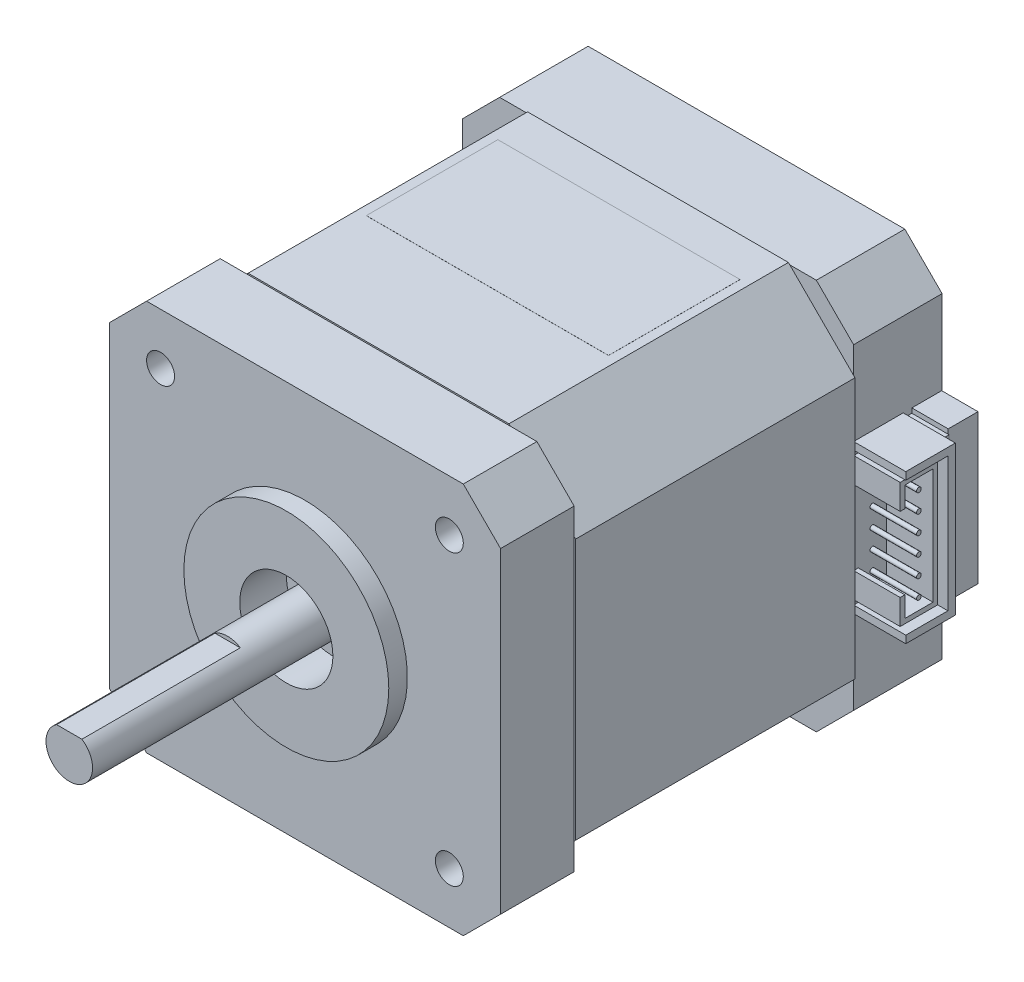
SolidWorks part; units mm, degrees
ref_plane "Front Plane" through (0, 0, 0) normal (0, 0, 1) x (1, 0, 0)
ref_plane "Top Plane" through (0, 0, 0) normal (0, 1, 0) x (1, 0, 0)
ref_plane "Right Plane" through (0, 0, 0) normal (1, 0, 0) x (0, 0, -1)
sketch "Sketch1" plane through (0, 0, 0) normal (0, 0, 1) x (1, 0, 0)
  line L0 (-17, 21) -> (-21, 17)
  line L1 (-17, -21) -> (17, -21)
  line L2 (-21, -17) -> (-21, 17)
  line L3 (-17, 21) -> (17, 21)
  line L4 (21, -17) -> (21, 17)
  line L5 (21, 17) -> (17, 21)
  line L6 (17, -21) -> (21, -17)
  line L12 (-21, -17) -> (-17, -21)
  point P0 (0, 0)
  point P15 (0, 0)
  dimension "D1" = 4
extrude "Boss-Extrude1" add sketch "Sketch1" along normal blind 9.5
sketch "Sketch2" plane through (0, 0, 9.5) normal (0, 0, 1) x (1, 0, 0)
  line L0 (14, 21.15) -> (21.15, 14)
  line L5 (-14, -21.15) -> (14, -21.15)
  line L6 (-21.15, -14) -> (-21.15, 14)
  line L7 (-14, 21.15) -> (14, 21.15)
  line L12 (21.15, -14) -> (21.15, 14)
  line L14 (17.5, -17.5) -> (17.575, -17.575) construction
  line L15 (-21.15, 14) -> (-14, 21.15)
  line L16 (21.15, -14) -> (14, -21.15)
  line L17 (-14, -21.15) -> (-21.15, -14)
  line L18 (17.5, 17.5) -> (17.575, 17.575) construction
  point P0 (0, 0)
  point P1 (0, 0)
  point P13 (0, 0)
  point P16 (0, 0)
  point P19 (0, 0)
  point P22 (0, 0)
  point P29 (0, 0)
  dimension "D1" = 4
  dimension "D5" = 4
extrude "Boss-Extrude2" add sketch "Sketch2" along normal blind 30
sketch "Sketch3" plane through (0, 0, 39.5) normal (0, 0, 1) x (1, 0, 0)
  line L0 (-17, 21) -> (17, 21)
  line L1 (17, 21) -> (21, 17)
  line L2 (21, 17) -> (21, -17)
  line L3 (21, -17) -> (17, -21)
  line L4 (17, -21) -> (-17, -21)
  line L5 (-17, -21) -> (-21, -17)
  line L6 (-21, -17) -> (-21, 17)
  line L7 (-21, 17) -> (-17, 21)
extrude "Boss-Extrude3" add sketch "Sketch3" along normal blind 7.9
sketch "Sketch5" plane through (0, 0, 47.4) normal (0, 0, 1) x (1, 0, 0)
  circle A0 centre (0, 0) radius 11
  circle A1 centre (0, 0) radius 5
  dimension "D1" = 22
  dimension "D2" = 10
extrude "Boss-Extrude4" add sketch "Sketch5" along normal blind 2
sketch "Sketch6" plane through (0, 0, 47.4) normal (0, 0, 1) x (1, 0, 0)
  circle A0 centre (0, 0) radius 5
extrude "Cut-Extrude1" cut sketch "Sketch6" against normal blind 3
sketch "Sketch7" plane through (0, 0, 44.4) normal (0, 0, 1) x (1, 0, 0)
  circle A0 centre (0, 0) radius 2.5
  dimension "D1" = 5
extrude "Boss-Extrude5" add sketch "Sketch7" along normal up to surface (5 mm away) up to face at (11, 0, 49.4)
sketch "Sketch8" plane through (0, 0, 49.4) normal (0, 0, 1) x (1, 0, 0)
  circle A0 centre (0, 0) radius 2.5
extrude "Boss-Extrude6" add sketch "Sketch8" along normal blind 23.3
sketch "Sketch9" plane through (0, 0, 72.7) normal (0, 0, 1) x (1, 0, 0)
  line L0 (-2.3166, 2.1) -> (3.6979, 2.1)
  line L1 (3.6979, 2.1) -> (-0.1236, 3.991)
  line L2 (-0.1236, 3.991) -> (-2.3166, 2.1)
extrude "Cut-Extrude2" cut sketch "Sketch9" against normal blind 17
sketch "Sketch10" plane through (0, 21.15, 0) normal (0, 1, 0) x (1, 0, 0)
  line L1 (-13, -13.6909) -> (13, -13.6909)
  line L3 (-13, -27.8113) -> (13, -27.8113)
  line L6 (-13, -13.6909) -> (-13, -27.8113)
  line L8 (13, -13.6909) -> (13, -27.8113)
extrude "Boss-Extrude7" add sketch "Sketch10" along normal blind 0.01
sketch "Sketch11" plane through (21, 0, 0) normal (1, 0, 0) x (0, 0, -1)
  line L1 (-3.2456, -8) -> (-0.0456, -8)
  line L3 (-3.2456, 8) -> (-0.0456, 8)
  line L5 (-3.2456, 8) -> (-3.2456, -8)
  line L7 (-0.0456, 8) -> (-0.0456, -8)
  point P0 (0, 0)
  dimension "D2" = 3.2
extrude "Boss-Extrude8" add sketch "Sketch11" along normal blind 3.9
sketch "Sketch12" plane through (21, 0, 0) normal (1, 0, 0) x (0, 0, -1)
  line L0 (-9.5, -14.15) -> (-9.5, 14.15) construction
  line L2 (-9.5, 7.479) -> (-9.5, 7.2)
  line L5 (-0.0456, 8) -> (-3.2456, 8) construction
  line L6 (-9.5, 7.2) -> (-4.9761, 7.2)
  line L9 (-4.1761, 7.2) -> (-4.1761, -7.2)
  line L10 (-4.1761, 8) -> (-9.5, 8)
  line L11 (-9.5, -14) -> (-9.5, 14) construction
  line L12 (-9.5, 7.479) -> (-9.5, 7.2)
  line L13 (-0.0456, 0) -> (6.3047, 0) construction
  line L14 (-0.0456, -8) -> (-0.0456, 8) construction
  line L15 (-9.5, -7.2) -> (-4.9761, -7.2)
  line L16 (-9.5, 7.2) -> (-9.5, 8)
  line L17 (-9.5, -7.2) -> (-9.5, -8)
  line L19 (-4.1761, -8) -> (-9.5, -8)
  line L20 (-4.9761, 7.2) -> (-4.9761, -7.2)
  line L21 (-4.1761, 8) -> (-4.1761, 7.2)
  line L22 (-4.1761, -7.2) -> (-4.1761, -8)
  dimension "D1" = 0.8
  dimension "D2" = 0.8
extrude "Boss-Extrude9" add sketch "Sketch12" along normal blind 5.6 contours L16 L10 L21 L9 L22 L19 L17 L15 L20 L6
sketch "Sketch13" plane through (21, 0, 0) normal (1, 0, 0) x (0, 0, -1)
  line L0 (-4.1761, 8) -> (-4.1761, -8) construction
  line L1 (-4.1761, 7.5) -> (-3.2456, 7.5)
  line L2 (-4.1761, 7.5) -> (-4.1761, -7.5)
  line L3 (-4.1761, -7.5) -> (-3.2456, -7.5)
  line L4 (-3.2456, 7.5) -> (-3.2456, -7.5)
  line L5 (-3.2456, 8) -> (-3.2456, -8) construction
  line L6 (-0.0456, 8) -> (-3.2456, 8) construction
  line L7 (-3.2456, -8) -> (-0.0456, -8) construction
  dimension "D1" = 0.5
  dimension "D2" = 0.5
extrude "Boss-Extrude10" add sketch "Sketch13" along normal up to surface (3.9 mm away) up to face at (24.9, 0, 1.6456)
sketch "Sketch14" plane through (24.9, 0, 0) normal (1, 0, 0) x (0, 0, -1)
  line L1 (-4.1761, 7.5) -> (-3.2456, 7.5)
  line L2 (-4.1761, 7.5) -> (-4.1761, -7.5)
  line L3 (-4.1761, -7.5) -> (-3.2456, -7.5)
  line L4 (-3.2456, 7.5) -> (-3.2456, -7.5)
extrude "Boss-Extrude11" add sketch "Sketch14" along normal blind 0.1
sketch "Sketch15" plane through (21, 0, 0) normal (1, 0, 0) x (0, 0, -1)
  line L0 (-5.9761, 6.2) -> (-9, 6.2)
  line L5 (0, 0) -> (5.9447, 0) construction
  line L6 (-9.5, -7.2) -> (-9.5, 7.2) construction
  line L7 (-9.5, 4) -> (-9, 4)
  line L9 (-9.5, -4) -> (-9, -4)
  line L11 (-9.5, 7.2) -> (-4.9761, 7.2) construction
  line L12 (-9, 6.7) -> (-5.4761, 6.7)
  line L13 (-9, 6.2) -> (-9, 4)
  line L14 (-9, -6.7) -> (-5.4761, -6.7)
  line L15 (-5.4761, 6.7) -> (-5.4761, -6.7)
  line L16 (-4.9761, 7.2) -> (-4.9761, -7.2) construction
  line L17 (-9, 6.7) -> (-9.5, 6.7)
  line L18 (-9.5, -7.2) -> (-9.5, 7.2) construction
  line L19 (-9.5, 6.7) -> (-9.5, 4)
  line L20 (-5.9761, 6.2) -> (-5.9761, -6.2)
  line L21 (-9.5, -7.2) -> (-4.9761, -7.2) construction
  line L22 (-9, -6.2) -> (-5.9761, -6.2)
  line L23 (-9.5, -4) -> (-9.5, -6.7)
  line L24 (-9.5, -6.7) -> (-9, -6.7)
  line L25 (-9, -4) -> (-9, -6.2)
  dimension "D1" = 4
  dimension "D2" = 4
  dimension "D4" = 0.5
  dimension "D5" = 0.5
  dimension "D6" = 0.5
  dimension "D7" = 0.5
  dimension "D8" = 0.5
  dimension "D9" = 0.5
extrude "Boss-Extrude12" add sketch "Sketch15" along normal blind 5
sketch "Sketch16" plane through (21, 0, 0) normal (1, 0, 0) x (0, 0, -1)
  line L0 (-7.4881, 6.2) -> (-7.4881, 5) construction
  line L1 (-9, 6.2) -> (-5.9761, 6.2) construction
  circle A0 centre (-7.4881, 5) radius 0.25
  circle A1 centre (-7.4881, 3) radius 0.25
  circle A2 centre (-7.4881, 1) radius 0.25
  circle A3 centre (-7.4881, -1) radius 0.25
  circle A4 centre (-7.4881, -3) radius 0.25
  circle A5 centre (-7.4881, -5) radius 0.25
  dimension "D2" = 0.5
  dimension "D1" = 1.2
  dimension "D3" = 6
extrude "Boss-Extrude13" add sketch "Sketch16" along normal blind 5
sketch "Sketch17" plane through (0, 0, 47.4) normal (0, 0, 1) x (1, 0, 0)
  circle A0 centre (-15.5, 15.5) radius 1.5
  circle A1 centre (15.5, 15.5) radius 1.5
  circle A2 centre (15.5, -15.5) radius 1.5
  circle A3 centre (-15.5, -15.5) radius 1.5
  point P0 (0, 0)
  point P13 (0, 0)
  dimension "D3" = 3
  dimension "D1" = 4
extrude "Cut-Extrude3" cut sketch "Sketch17" against normal blind 5.5
sketch "Sketch18" plane through (0, 0, 0) normal (0, 0, -1) x (-1, 0, 0)
  circle A0 centre (-15.5, 15.5) radius 3.25
  circle A1 centre (15.5, 15.5) radius 3.25
  circle A2 centre (15.5, -15.5) radius 3.25
  circle A3 centre (-15.5, -15.5) radius 3.25
  point P0 (0, 0)
  point P13 (0, 0)
  dimension "D3" = 6.5
  dimension "D1" = 4
extrude "Cut-Extrude4" cut sketch "Sketch18" against normal blind 3
sketch "Sketch20" plane through (0, 0, 3) normal (0, 0, -1) x (-1, 0, 0)
  circle A0 centre (-15.5, 15.5) radius 1.5
  circle A1 centre (15.5, 15.5) radius 1.5
  circle A2 centre (-15.5, -15.5) radius 1.5
  circle A3 centre (15.5, -15.5) radius 1.5
  dimension "D1" = 3
  dimension "D2" = 3
  dimension "D3" = 3
  dimension "D4" = 3
extrude "Cut-Extrude5" cut sketch "Sketch20" against normal blind 4
sketch "Sketch21" plane through (0, 0, 0) normal (0, 0, -1) x (-1, 0, 0)
  circle A0 centre (0, 0) radius 4.5
  dimension "D1" = 9
extrude "Cut-Extrude6" cut sketch "Sketch21" against normal blind 4
